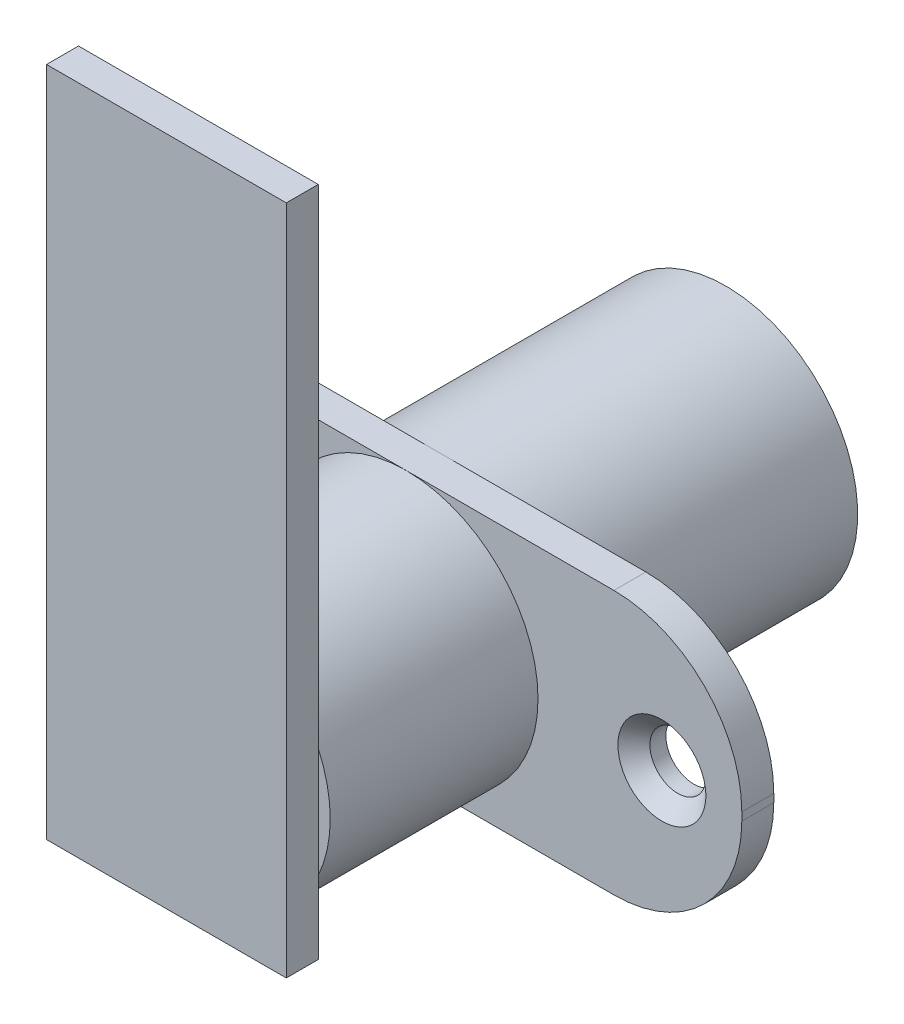
SolidWorks part; units mm, degrees
ref_plane "Plan de face" through (0, 0, 0) normal (0, 0, 1) x (1, 0, 0)
ref_plane "Plan de dessus" through (0, 0, 0) normal (0, 1, 0) x (1, 0, 0)
ref_plane "Plan de droite" through (0, 0, 0) normal (1, 0, 0) x (0, 0, -1)
sketch "Esquisse1" plane through (0, 0, 0) normal (0, 0, 1) x (1, 0, 0)
  line L1 (8, 0) -> (34, 0)
  line L2 (0, -8) -> (0, -8.5)
  line L3 (8, -16.5) -> (34, -16.5)
  line L4 (42, -8) -> (42, -8.5)
  circle A0 centre (5, -8.25) radius 1.75
  circle A1 centre (37, -8.25) radius 1.75
  arc A2 (42, -8.5) -> (34, -16.5) centre (34, -8.5) cw
  arc A3 (0, -8.5) -> (8, -16.5) centre (8, -8.5) ccw
  arc A4 (34, 0) -> (42, -8) centre (34, -8) cw
  arc A5 (0, -8) -> (8, 0) centre (8, -8) cw
  point P19 (0, 0)
  dimension "D1" = 3.5
  dimension "D2" = 3.5
  dimension "D8" = 8
  dimension "D3" = 42
  dimension "D4" = 16.5
  dimension "D5" = 8.25
  dimension "D6" = 32
  dimension "D7" = 5
  dimension "D9" = 8.25
extrude "Boss.-Extru.1" add sketch "Esquisse1" along normal blind 2
sketch "Esquisse2" plane through (0, 0, 0) normal (0, 0, -1) x (-1, 0, 0)
  line L0 (-21, -16.5) -> (-21, 0)
  line L1 (-8, -16.5) -> (-34, -16.5) construction
  line L2 (-34, 0) -> (-8, 0) construction
  line L3 (-42, -8.25) -> (0, -8.25)
  line L4 (-42, -8.5) -> (-42, -8) construction
  line L5 (0, -8) -> (0, -8.5) construction
  circle A0 centre (-21, -8.25) radius 8.25
  dimension "D1" = 16.5
extrude "Boss.-Extru.2" add sketch "Esquisse2" along normal blind 18 and the other way blind 15 contours L3 A0 L0 | L0 A0 L3 | L3 A0 L0 | L0 A0 L3 region at (24.5014, -11.7514, 0) region at (17.4986, -11.7514, 0) region at (24.5014, -4.7486, 0) region at (17.4986, -4.7486, 0)
chamfer "Chanfrein1" distance 1 angle 45 2 edges at (38.75, -8.25, 2) (6.75, -8.25, 2)
sketch "Esquisse3" plane through (0, 0, 15) normal (0, 0, 1) x (1, 0, 0)
  line L1 (13.5, -16.25) -> (28.5, -16.25)
  line L2 (13.5, -16.25) -> (13.5, 25.75)
  line L3 (13.5, 25.75) -> (28.5, 25.75)
  line L4 (28.5, -16.25) -> (28.5, 25.75)
  circle A0 centre (21, -8.25) radius 8.25 construction
  dimension "D1" = 15
  dimension "D2" = 8
  dimension "D3" = 42
  dimension "D4" = 7.5
extrude "Boss.-Extru.3" add sketch "Esquisse3" along normal blind 2
